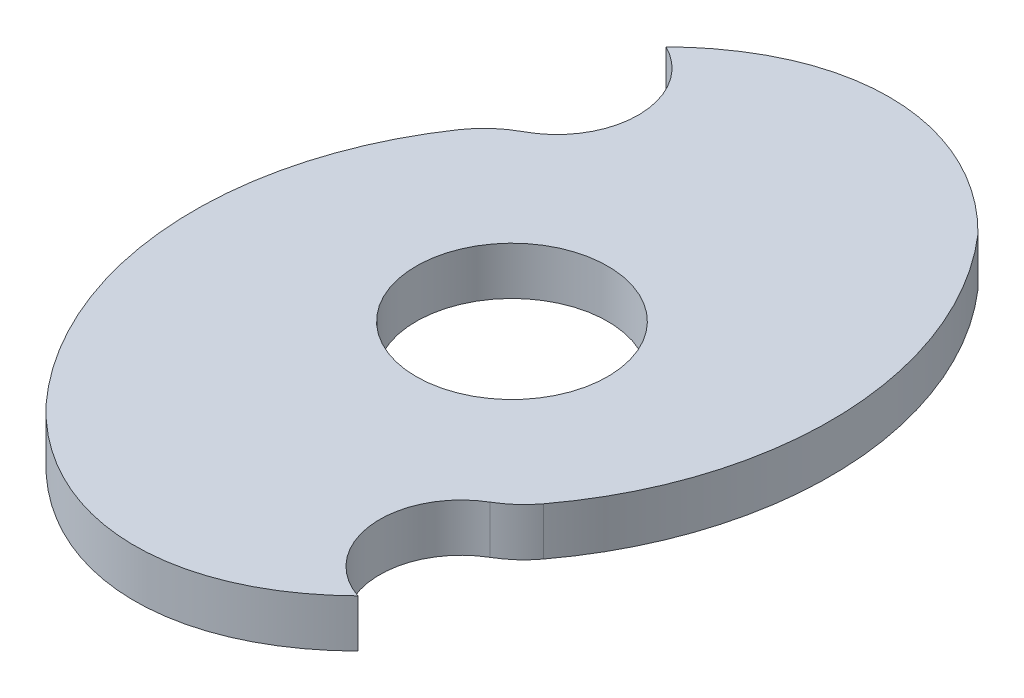
SolidWorks part; units mm, degrees
ref_plane "Front Plane" through (0, 0, 0) normal (0, 0, 1) x (1, 0, 0)
ref_plane "Top Plane" through (0, 0, 0) normal (0, 1, 0) x (1, 0, 0)
ref_plane "Right Plane" through (0, 0, 0) normal (1, 0, 0) x (0, 0, -1)
other "Center of Mass"
sketch "Sketch2" plane through (0, 0, 0) normal (0, 1, 0) x (1, 0, 0)
  line L0 (52.4071, 30.4049) -> (52.4984, 30.3816)
  line L1 (31.58, 65.725) -> (33.5479, 65.725)
  line L3 (-33.3698, -65.725) -> (-31.58, -65.725)
  line L4 (33.5479, 65.725) -> (33.5479, 63.7588)
  line L5 (32.8908, 64.4344) -> (33.5479, 65.725) construction
  line L6 (-33.3698, -65.725) -> (-32.7732, -64.5532) construction
  line L8 (-52.4984, -30.1076) -> (-52.4984, -29.8943)
  line L9 (-52.4984, -29.8943) -> (-52.5633, -29.8943)
  line L10 (52.4984, 30.3816) -> (52.4984, 30.1076)
  line L12 (-52.4984, -29.8943) -> (-52.5537, -29.926) construction
  line L14 (-33.5479, -63.7588) -> (-33.3698, -65.725)
  line L16 (52.4269, 30.3406) -> (52.4984, 30.3816) construction
  arc A0 (-33.1118, 35.4968) -> (-33.5535, 65.7315) centre (-41.1045, 50.5006) ccw
  arc A1 (30.3971, -34.9727) -> (33.5535, -65.7315) centre (39.0082, -49.6304) ccw
  arc A2 (-40.2422, 29.0986) -> (-33.5479, -63.7588) centre (21.759, -13.1016) ccw
  arc A3 (32.8908, 64.4344) -> (36.2689, -29.725) centre (-23.7406, 15.2624) cw
  arc A4 (-40.2422, 29.0986) -> (-33.1118, 35.4968) centre (-23.7085, 17.8452) cw
  arc A5 (30.3971, -34.9727) -> (36.2689, -29.725) centre (20.2664, -17.7284) ccw
  circle A6 centre (0, 0) radius 20
  ellipse E0 centre (0, 0) end of major axis (2.4604, -79.9622) minor radius 57.1429 (-52.5633, -29.8943) -> (-52.4984, -30.1076) ccw
  ellipse E1 centre (0, 0) end of major axis (2.4604, -79.9622) minor radius 57.1429 (52.4984, 30.1076) -> (52.4071, 30.4049) ccw
  ellipse E2 centre (0, 0) end of major axis (2.4604, -79.9622) minor radius 57.1429 (33.5479, 63.7588) -> (-33.5535, 65.7315) ccw
  ellipse E3 centre (0, 0) end of major axis (2.4604, -79.9622) minor radius 57.1429 (-33.5479, -63.7588) -> (33.5535, -65.7315) ccw
  point P46 (0, 0)
  dimension "D1" = 20
  dimension "D2" = 20
extrude "Boss-Extrude1" add sketch "Sketch2" along normal blind 10 contours A2 E3 A1 A5 A3 E2 A0 A4 A6 region at (30.8995, 0, -63.723)
